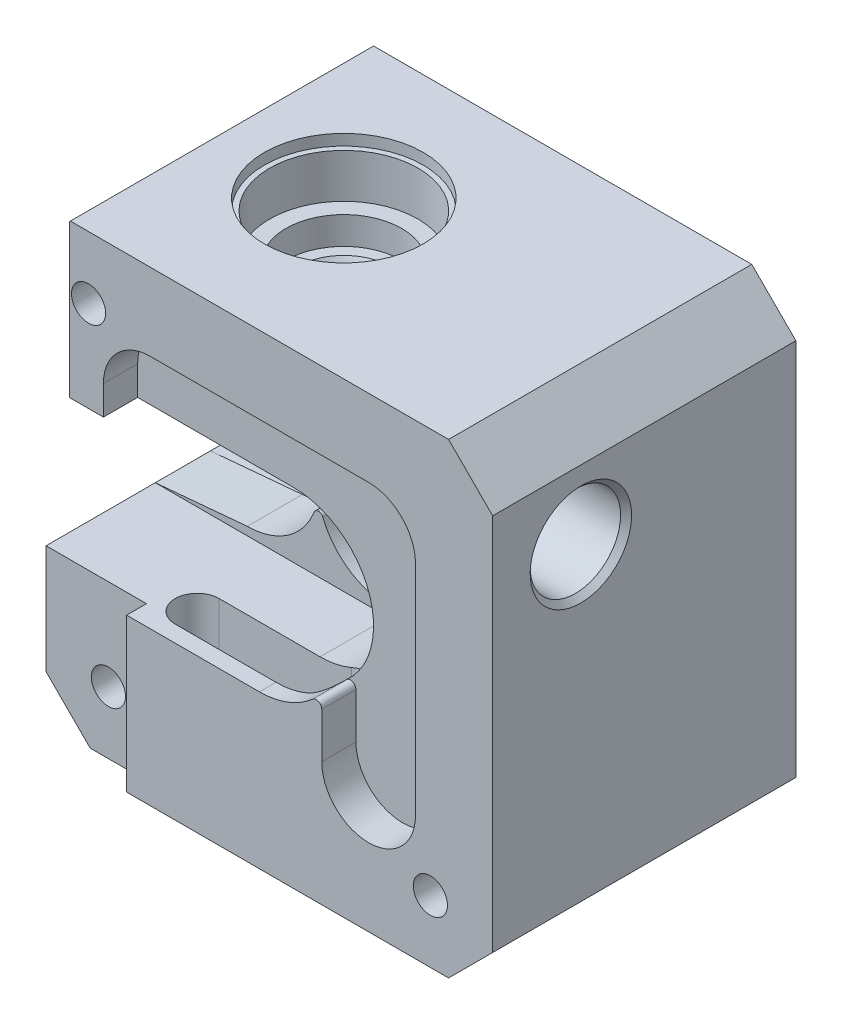
SolidWorks part; units mm, degrees
material "aluminio"
ref_plane "Alzado" through (0, 0, 0) normal (0, 0, 1) x (1, 0, 0)
ref_plane "Planta" through (0, 0, 0) normal (0, 1, 0) x (1, 0, 0)
ref_plane "Vista lateral" through (0, 0, 0) normal (1, 0, 0) x (0, 0, -1)
sketch "Croquis1" plane through (0, 0, 0) normal (0, 0, 1) x (1, 0, 0)
  line L1 (0, 0) -> (42.3, 0)
  line L2 (0, 0) -> (0, 42.3)
  line L3 (0, 42.3) -> (42.3, 42.3)
  line L4 (42.3, 0) -> (42.3, 42.3)
  dimension "D1" = 42.3
  dimension "D2" = 42.3
extrude "Saliente-Extruir1" add sketch "Croquis1" along normal blind 28
chamfer "Chaflán1" distance 4 angle 45 4 edges at (42.3, 0, 14) (0, 0, 14) (42.3, 42.3, 14) (0, 42.3, 14)
sketch "Croquis5" plane through (0, 0, 28) normal (0, 0, 1) x (1, 0, 0)
  line L0 (0, 38.3) -> (0, 4) construction
  line L1 (0, 28.4) -> (28.4, 28.4)
  line L2 (0, 28.4) -> (0, 13.9)
  line L3 (0, 13.9) -> (28.4, 13.9)
  line L4 (28.4, 28.4) -> (28.4, 13.9)
  line L5 (42.3, 21.15) -> (28.4, 21.15) construction
  line L6 (42.3, 4) -> (42.3, 38.3) construction
  dimension "D1" = 14.5
  dimension "D2" = 28.4
extrude "Cortar-Extruir4" cut sketch "Croquis5" against normal up to surface (28 mm away) up to face at (21.15, 21.15, 0)
sketch "Croquis6" plane through (0, 0, 0) normal (-1, 0, 0) x (0, 0, 1)
  line L0 (0, 28.4) -> (28, 28.4) construction
  line L1 (11.7, 28.4) -> (16.7, 28.4)
  line L2 (11.7, 28.4) -> (11.7, 13.9)
  line L3 (11.7, 13.9) -> (16.7, 13.9)
  line L4 (16.7, 28.4) -> (16.7, 13.9)
  line L6 (0, 13.9) -> (28, 13.9) construction
  line L7 (0, 13.9) -> (0, 28.4) construction
  dimension "D1" = 5
  dimension "D2" = 11.7
extrude "Saliente-Extruir2" add sketch "Croquis6" against normal up to surface (28.4 mm away) up to face at (28.4, 21.15, 14)
sketch "Croquis7" plane through (0, 0, 16.7) normal (0, 0, 1) x (1, 0, 0)
  line L0 (0, 21.15) -> (8.35, 21.15) construction
  line L1 (0, 13.9) -> (0, 28.4) construction
  line L2 (0, 27.65) -> (8.35, 27.65)
  line L3 (0, 14.65) -> (8.35, 14.65)
  line L4 (0, 13.9) -> (0, 4) construction
  line L5 (14.7726, 22.15) -> (14.8286, 22.15)
  line L6 (21.15, 21.15) -> (42.3, 21.15) construction
  line L7 (42.3, 4) -> (42.3, 38.3) construction
  line L11 (14.7726, 20.15) -> (14.8286, 20.15)
  arc A0 (14.8286, 20.15) -> (14.8286, 22.15) centre (21.15, 21.15) ccw
  arc A1 (0, 27.65) -> (0, 14.65) centre (0, 21.15) ccw
  arc A2 (8.35, 14.65) -> (14.7726, 20.15) centre (8.35, 21.15) ccw
  arc A3 (14.7726, 22.15) -> (8.35, 27.65) centre (8.35, 21.15) ccw
  dimension "D1" = 6.5
  dimension "D2" = 12.8
  dimension "D6" = 6.5
  dimension "D3" = 12.8
  dimension "D4" = 21.15
  dimension "D5" = 2
extrude "Cortar-Extruir5" cut sketch "Croquis7" against normal up to next
sketch "Croquis3" plane through (0, 42.3, 0) normal (0, 1, 0) x (1, 0, 0)
  line L0 (4, -14.2) -> (14.6, -14.2) construction
  line L2 (0, -28) -> (0, 0) construction
  line L3 (38.3, 0) -> (4, 0) construction
  circle A0 centre (14.6, -14.2) radius 1.9
  dimension "D1" = 3.8
  dimension "D2" = 14.6
  dimension "D3" = 14.2
extrude "Cortar-Extruir2" cut sketch "Croquis3" against normal through all
sketch "Croquis8" plane through (0, 0, 11.7) normal (0, 0, -1) x (-1, 0, 0)
  line L0 (-8.35, 14.65) -> (0, 13.9)
  line L1 (0, 13.9) -> (0, 14.65)
  line L2 (0, 14.65) -> (-8.35, 14.65)
  line L3 (0, 28.4) -> (-8.35, 27.65)
  line L4 (-8.35, 27.65) -> (0, 27.65)
  line L5 (0, 27.65) -> (0, 28.4)
extrude "Cortar-Extruir6" cut sketch "Croquis8" against normal blind 20
sketch "Croquis9" plane through (0, 0, 0) normal (0, 0, -1) x (-1, 0, 0)
  line L0 (-36.65, 36.65) -> (-5.65, 36.65) construction
  line L1 (-5.65, 36.65) -> (-5.65, 5.65) construction
  line L2 (-5.65, 5.65) -> (-36.65, 5.65) construction
  line L3 (-36.65, 5.65) -> (-36.65, 36.65) construction
  line L4 (-21.15, 36.65) -> (-21.15, 42.3) construction
  line L5 (-38.3, 42.3) -> (-4, 42.3) construction
  line L6 (-42.3, 21.15) -> (-36.65, 21.15) construction
  line L7 (-42.3, 4) -> (-42.3, 38.3) construction
  circle A0 centre (-36.65, 36.65) radius 1.55 construction
  circle A1 centre (-5.65, 36.65) radius 1.55
  circle A2 centre (-5.65, 5.65) radius 1.55
  circle A3 centre (-36.65, 5.65) radius 1.55
  dimension "D2" = 3.1
  dimension "D1" = 31
extrude "Cortar-Extruir7" cut sketch "Croquis9" against normal up to surface (28 mm away) up to face at (18.8333, 21.15, 28)
sketch "Croquis10" plane through (0, 42.3, 0) normal (0, 1, 0) x (1, 0, 0)
  circle A0 centre (14.6, -14.2) radius 6.725
  dimension "D1" = 13.45
extrude "Cortar-Extruir8" cut sketch "Croquis10" against normal blind 5
sketch "Croquis11" plane through (0, 37.3, 0) normal (0, 1, 0) x (1, 0, 0)
  circle A0 centre (14.6, -14.2) radius 5.25
  dimension "D1" = 10.5
extrude "Cortar-Extruir9" cut sketch "Croquis11" against normal blind 2.5
sketch "Croquis12" plane through (0, 34.8, 0) normal (0, 1, 0) x (1, 0, 0)
  circle A0 centre (14.6, -14.2) radius 3.25
  dimension "D1" = 6.5
extrude "Cortar-Extruir10" cut sketch "Croquis12" against normal blind 6
sketch "Croquis15" plane through (0, 42.3, 0) normal (0, 1, 0) x (1, 0, 0)
  circle A0 centre (14.6, -14.2) radius 7.2
  dimension "D1" = 14.4
extrude "Cortar-Extruir13" cut sketch "Croquis15" against normal blind 1
chamfer "Chaflán2" distance 1 angle 60 1 edges at (14.6, 34.8, 17.45) first distance on face at (14.6, 34.8, 17.45)
ref_plane "Plano1" through (0, 21.15, 0) normal (0, 1, 0) x (1, 0, 0)
mirror "Simetría1" about plane through (0, 21.15, 0) normal (0, 1, 0) of "Cortar-Extruir13", "Cortar-Extruir8", "Cortar-Extruir9", "Cortar-Extruir10"
chamfer "Chaflán4" distance 1 angle 60 1 edges at (14.6, 7.5, 17.45) first distance on face at (14.6, 7.5, 17.45)
chamfer "Chaflán5" distance 0.7 angle 60 1 edges at (14.6, 13.5, 12.3) first distance on face at (14.6, 13.5, 17.45)
chamfer "Chaflán6" [suppressed] distance 0.5 angle 60
ref_plane "Plano2" through (0, 0, 14) normal (0, 0, 1) x (1, 0, 0)
sketch "Croquis18" plane through (0, 42.3, 0) normal (0, 1, 0) x (1, 0, 0)
  line L0 (12, -24.5) -> (24, -24.5) construction
  line L1 (12, -22.5) -> (24, -22.5) construction
  line L2 (12, -26.5) -> (24, -26.5) construction
  line L3 (38.3, -28) -> (4, -28) construction
  line L4 (4, -14) -> (38.3, -14) construction
  line L5 (0, -28) -> (0, 0) construction
  line L6 (4, 0) -> (4, -28) construction
  line L7 (38.3, -28) -> (38.3, 0) construction
  line L8 (12, -3.5) -> (24, -3.5) construction
  line L9 (12, -5.5) -> (24, -5.5)
  line L10 (12, -1.5) -> (24, -1.5)
  arc A0 (12, -22.5) -> (12, -26.5) centre (12, -24.5) ccw construction
  arc A1 (24, -26.5) -> (24, -22.5) centre (24, -24.5) ccw construction
  arc A2 (12, -5.5) -> (12, -1.5) centre (12, -3.5) cw
  arc A3 (24, -1.5) -> (24, -5.5) centre (24, -3.5) cw
  point P2 (18, -24.5)
  point P19 (18, -3.5)
  dimension "D1" = 2
  dimension "D2" = 12
  dimension "D3" = 1.5
  dimension "D4" = 12
extrude "Cortar-Extruir17" cut sketch "Croquis18" against normal up to surface (13.9 mm away) from surface at -28.4 up to face at (14.6, 0, 21.4) starting at face at (14.2, 13.9, 5.85)
sketch "Croquis21" plane through (0, 0, 16.7) normal (0, 0, 1) x (1, 0, 0)
  line L1 (14.5014, 23.25) -> (15.1043, 23.25)
  line L2 (14.5014, 23.25) -> (14.5014, 19.05)
  line L3 (14.5014, 19.05) -> (15.1043, 19.05)
  line L4 (15.1043, 23.25) -> (15.1043, 19.05)
  arc A0 (8.35, 14.65) -> (14.7726, 20.15) centre (8.35, 21.15) ccw construction
  circle A1 centre (21.15, 21.15) radius 6.4 construction
  dimension "D1" = 4.2
  dimension "D2" = 0.6029
extrude "Cortar-Extruir19" cut sketch "Croquis21" against normal through all
sketch "Croquis22" plane through (0, 0, 0) normal (-1, 0, 0) x (0, 0, 1)
  line L2 (8, 32.3) -> (8, 31.8) construction
  line L3 (9.55, 32.3) -> (9.55, 31.8) construction
  line L4 (6.45, 32.3) -> (6.45, 31.8) construction
  line L5 (0, 38.3) -> (0, 28.4) construction
  line L6 (0, 42.3) -> (28, 42.3) construction
  arc A0 (9.55, 32.3) -> (6.45, 32.3) centre (8, 32.3) ccw construction
  arc A1 (6.45, 31.8) -> (9.55, 31.8) centre (8, 31.8) ccw construction
  circle A2 centre (8, 32.05) radius 2.5
  point P2 (8, 32.05)
  dimension "D1" = 1.55
  dimension "D5" = 5
  dimension "D2" = 0.5
  dimension "D3" = 8
  dimension "D4" = 10
extrude "Cortar-Extruir20" cut sketch "Croquis22" against normal through all
fillet "Redondeo1" radius 0.4 8 edges at (14.5014, 19.05, 12.0013) (15.1043, 19.05, 12.0341) (15.1043, 19.05, 16.3659) (14.5014, 19.05, 16.3987) (15.1043, 23.25, 16.3659) (15.1043, 23.25, 12.0341) (14.5014, 23.25, 12.0013) (14.5014, 23.25, 16.3987)
sketch "Croquis25" plane through (0, 42.3, 0) normal (0, 1, 0) x (1, 0, 0)
  line L0 (42.3, 0) -> (42.3, -28) construction
  line L1 (0, -28) -> (42.3, -28)
  line L2 (0, -28) -> (0, -27.5)
  line L3 (0, -27.5) -> (42.3, -27.5)
  line L4 (42.3, -28) -> (42.3, -27.5)
  dimension "D1" = 0.5
extrude "Cortar-Extruir23" cut sketch "Croquis25" against normal through all
sketch "Croquis34" plane through (0, 0, 0) normal (-1, 0, 0) x (0, 0, 1)
  line L0 (27.5, 0) -> (0, 0) construction
  line L1 (0, 13.9) -> (1.8, 13.9)
  line L2 (0, 13.9) -> (0, 0)
  line L3 (0, 0) -> (1.8, 0)
  line L4 (1.8, 13.9) -> (1.8, 0)
  line L5 (16.7, 13.9) -> (27.5, 13.9) construction
  line L6 (19.8, 13.9) -> (24.3, 13.9)
  line L7 (19.8, 13.9) -> (19.8, 0)
  line L8 (19.8, 0) -> (24.3, 0)
  line L9 (24.3, 13.9) -> (24.3, 0)
  dimension "D1" = 1.8
  dimension "D2" = 19.8
  dimension "D3" = 4.5
extrude "Cortar-Extruir28" cut sketch "Croquis34" against normal blind 9.1
fillet "Redondeo6" radius 7.25 4 edges at (28.4, 28.4, 5.85) (28.4, 13.9, 5.85) (28.4, 13.9, 22.1) (28.4, 28.4, 22.1)
sketch "Croquis35" plane through (0, 0, 0) normal (-1, 0, 0) x (0, 0, 1)
  line L0 (0, 28.4) -> (0, 21.15) construction
  line L2 (24.7, 27.4) -> (24.7, 29.15)
  line L3 (0, 27.4) -> (0, 42.3)
  line L4 (0, 42.3) -> (12.7, 42.3)
  line L5 (0, 42.3) -> (27.5, 42.3) construction
  line L6 (12.7, 42.3) -> (12.7, 37.65)
  line L7 (12.7, 37.65) -> (16.2, 37.65)
  line L8 (27.5, 28.4) -> (27.5, 38.3) construction
  line L9 (0, 27.4) -> (24.7, 27.4)
  line L10 (0, 28.4) -> (11.7, 28.4) construction
  arc A0 (16.2, 37.65) -> (24.7, 29.15) centre (16.2, 29.15) cw
  dimension "D1" = 8.5
  dimension "D2" = 2.8
  dimension "D3" = 4.65
  dimension "D4" = 12.7
  dimension "D5" = 1
extrude "Cortar-Extruir29" cut sketch "Croquis35" against normal blind 3.9
fillet "Redondeo7" radius 2 1 edges at (1.95, 37.65, 12.7)
sketch "Croquis24" plane through (42.3, 0, 0) normal (1, 0, 0) x (0, 0, -1)
  circle A0 centre (-8, 32.05) radius 4.1
  dimension "D1" = 8.2
extrude "Cortar-Extruir22" cut sketch "Croquis24" against normal blind 17
chamfer "Chaflán7" distance 0.5 angle 45 1 edges at (42.3, 36.15, 8)
sketch "Croquis36" plane through (0, 0, 0) normal (0, 0, -1) x (-1, 0, 0)
  line L0 (-35.2995, 31.0495) -> (-35.2995, 11.2505)
  line L1 (-31.0495, 35.2995) -> (-11.2505, 35.2995)
  line L2 (-24, 0) -> (-24, 14.4837) construction
  line L3 (-26.7995, 11.2505) -> (-26.7995, 26.7995)
  line L4 (-26.7995, 26.7995) -> (-11.2505, 26.7995)
  line L5 (-7.0005, 31.0495) -> (-7.0005, 28.4)
  line L6 (-21.15, 28.4) -> (-3.9, 28.4) construction
  line L10 (-3.9, 28.4) -> (-3.9, 42.2)
  line L11 (-3.9, 42.2) -> (-4, 42.3)
  line L12 (-4, 42.3) -> (-38.3, 42.3)
  line L13 (-38.3, 42.3) -> (-42.3, 38.3)
  line L14 (-42.3, 38.3) -> (-42.3, 4)
  line L15 (-42.3, 4) -> (-38.3, 0)
  line L16 (-38.3, 0) -> (-9.1, 0)
  line L17 (-9.1, 0) -> (-9.1, 13.9)
  line L18 (-9.1, 13.9) -> (-21.15, 13.9)
  line L19 (-21.15, 28.4) -> (-3.9, 28.4)
  line L20 (-3.9, 28.4) -> (-3.9, 42.2)
  line L21 (-3.9, 42.2) -> (-4, 42.3)
  line L22 (-4, 42.3) -> (-38.3, 42.3)
  line L23 (-38.3, 42.3) -> (-42.3, 38.3)
  line L24 (-42.3, 38.3) -> (-42.3, 4)
  line L25 (-42.3, 4) -> (-38.3, 0)
  line L26 (-38.3, 0) -> (-9.1, 0)
  line L27 (-9.1, 0) -> (-9.1, 13.9)
  line L28 (-9.1, 13.9) -> (-24, 13.9)
  circle A0 centre (-31.0495, 11.2505) radius 2.75 construction
  circle A1 centre (-11.2505, 31.0495) radius 2.75 construction
  arc A2 (-28.4, 21.15) -> (-21.15, 13.9) centre (-21.15, 21.15) ccw
  arc A3 (-21.15, 28.4) -> (-28.4, 21.15) centre (-21.15, 21.15) ccw
  arc A4 (-28.4, 21.15) -> (-21.15, 13.9) centre (-21.15, 21.15) ccw
  arc A5 (-21.15, 28.4) -> (-28.4, 21.15) centre (-21.15, 21.15) ccw
  circle A6 centre (-31.0495, 31.0495) radius 2.75 construction
  circle A7 centre (-31.0495, 11.2505) radius 2.75 construction
  circle A8 centre (-11.2505, 31.0495) radius 2.75 construction
  circle A9 centre (-31.0495, 31.0495) radius 2.75 construction
  circle A10 centre (-11.2505, 31.0495) radius 4.25
  circle A11 centre (-31.0495, 31.0495) radius 4.25
  circle A12 centre (-31.0495, 11.2505) radius 4.25
  dimension "D2" = 8.5
  dimension "D1" = 0
extrude "Cortar-Extruir30" cut sketch "Croquis36" against normal blind 3.1
fillet "Redondeo10" radius 0.5 1 edges at (26.7995, 16.6062, 1.55) type face fillet first side face at (24.7244, 15.8778, 4.3388) second side face at (26.7995, 13.9284, 1.55)
sketch "Croquis37" plane through (0, 0, 11.7) normal (0, 0, -1) x (-1, 0, 0)
  line L0 (-22, 27.55) -> (-21.15, 27.55)
  line L1 (-22, 14.75) -> (-21.15, 14.75)
  arc A0 (-21.15, 28.4) -> (-28.4, 21.15) centre (-21.15, 21.15) ccw construction
  arc A1 (-21.15, 28.4) -> (-28.4, 21.15) centre (-21.15, 21.15) ccw construction
  arc A2 (-15.1982, 23.5029) -> (-15.1982, 18.7971) centre (-21.15, 21.15) ccw construction
  arc A3 (-15.1982, 23.5029) -> (-15.1982, 18.7971) centre (-21.15, 21.15) ccw construction
  arc A4 (-22, 27.55) -> (-22, 14.75) centre (-22, 21.15) ccw
  arc A5 (-21.15, 14.75) -> (-21.15, 27.55) centre (-21.15, 21.15) ccw
  point P10 (-28.4, 21.15)
  dimension "D1" = 0.85
extrude "Cortar-Extruir31" cut sketch "Croquis37" against normal through all both and the other way through all
ref_plane "Plano3" through (0, 0, 13.75) normal (0, 0, -1) x (-1, 0, 0)
mirror "Simetría2" about plane through (0, 0, 13.75) normal (0, 0, -1) of bodies 143 141
delete or keep bodies "Sólido-Eliminar/Conservar 1" type delete bodies bodies 143
